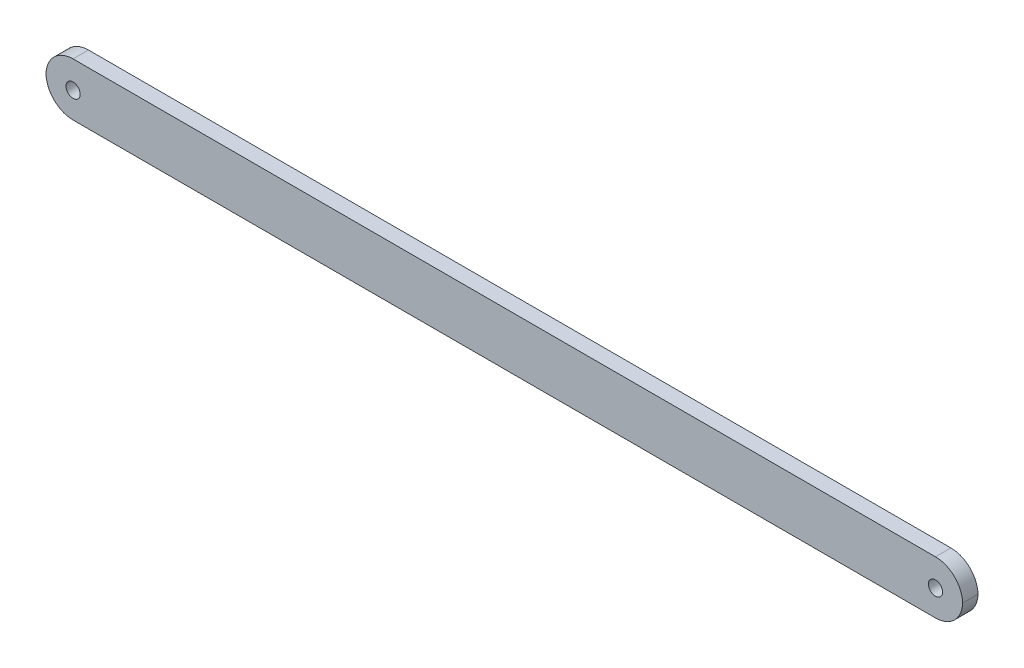
SolidWorks part; units mm, degrees
material "Acrylic (Medium-high impact)"
ref_plane "Front Plane" through (0, 0, 0) normal (0, 0, 1) x (1, 0, 0)
ref_plane "Top Plane" through (0, 0, 0) normal (0, 1, 0) x (1, 0, 0)
ref_plane "Right Plane" through (0, 0, 0) normal (1, 0, 0) x (0, 0, -1)
sketch "Sketch1" plane through (0, 0, 0) normal (0, 0, 1) x (1, 0, 0)
  line L1 (-94.488, -5.461) -> (94.488, -5.461)
  line L2 (-94.488, -5.461) -> (-94.488, 5.461)
  line L3 (-94.488, 5.461) -> (94.488, 5.461)
  line L4 (94.488, -5.461) -> (94.488, 5.461)
  line L5 (-94.488, -5.461) -> (94.488, 5.461) construction
  line L6 (-94.488, 5.461) -> (94.488, -5.461) construction
  point P0 (0, 0)
  dimension "D1" = 188.976
  dimension "D2" = 10.922
extrude "Boss-Extrude1" add sketch "Sketch1" along normal blind 3.175
fillet "Fillet1" radius 5.588 4 edges at (-94.488, -5.461, 1.5875) (-94.488, 5.461, 1.5875) (94.488, -5.461, 1.5875) (94.488, 5.461, 1.5875)
sketch "Sketch2" plane through (0, 0, 3.175) normal (0, 0, 1) x (1, 0, 0)
  circle A0 centre (-88.9, -0.127) radius 1.4605
  circle A1 centre (88.9, -0.127) radius 1.4605
  dimension "D1" = 2.921
  dimension "D2" = 2.921
extrude "Cut-Extrude1" cut sketch "Sketch2" against normal through all
